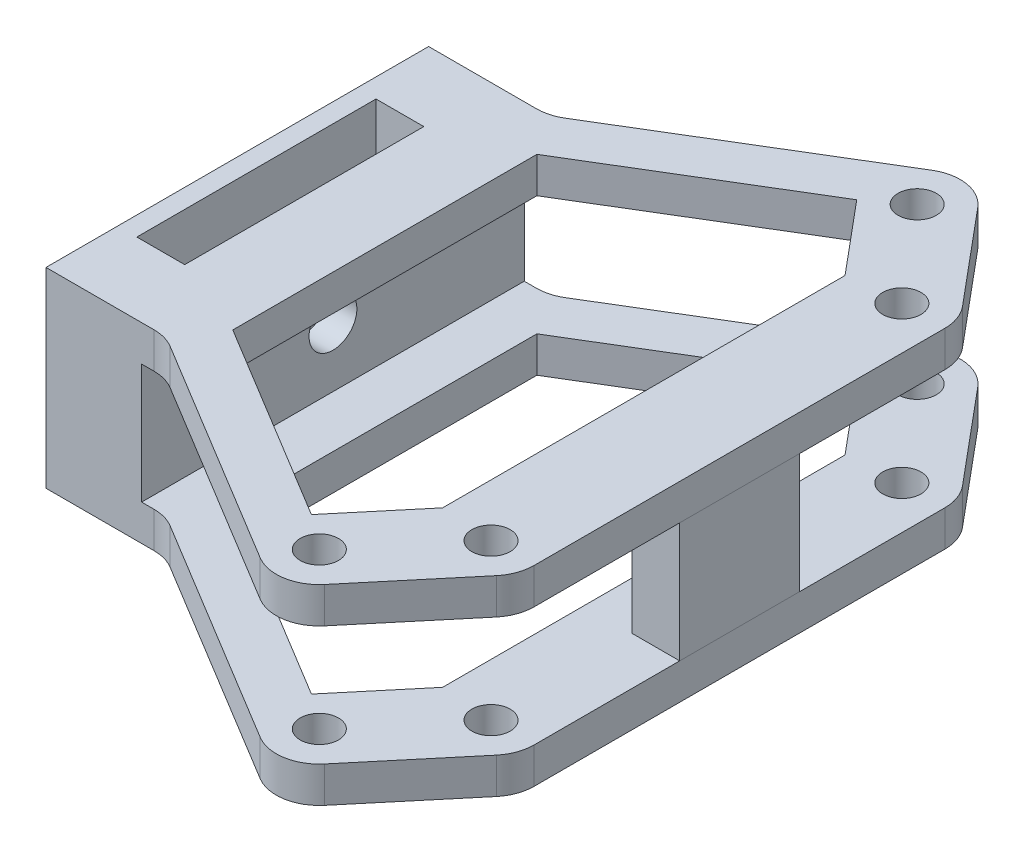
SolidWorks part; units mm, degrees
ref_plane "Front Plane" through (0, 0, 0) normal (0, 0, 1) x (1, 0, 0)
ref_plane "Top Plane" through (0, 0, 0) normal (0, 1, 0) x (1, 0, 0)
ref_plane "Right Plane" through (0, 0, 0) normal (1, 0, 0) x (0, 0, -1)
sketch "Sketch2" plane through (0, 0, 0) normal (0, 1, 0) x (1, 0, 0)
  line L0 (0, 0) -> (-170.473, 0) construction
  line L1 (0, -42.95) -> (0, 42.95)
  line L2 (-2.0962, 48.7238) -> (-18.4462, 68.2738)
  line L3 (-30.0101, 70.1996) -> (-77.759, 41.3004)
  line L4 (-82.419, 40) -> (-105, 40)
  line L5 (-105, 40) -> (-105, -40)
  line L6 (-74.15, -31.7958) -> (-74.15, 31.7958)
  line L7 (-74.15, 31.7958) -> (-32.4907, 57.0093)
  line L8 (-32.4907, 57.0093) -> (-20, 42.074)
  line L9 (-20, 42.074) -> (-20, -42.074)
  line L10 (-82.419, -40) -> (-105, -40)
  line L11 (-32.4907, -57.0093) -> (-20, -42.074)
  line L12 (-74.15, -31.7958) -> (-32.4907, -57.0093)
  line L13 (-30.0101, -70.1996) -> (-77.759, -41.3004)
  line L14 (-2.0962, -48.7238) -> (-18.4462, -68.2738)
  line L16 (-101, -25) -> (-91, -25)
  line L17 (-101, -25) -> (-101, 25)
  line L18 (-101, 25) -> (-91, 25)
  line L19 (-91, -25) -> (-91, 25)
  arc A0 (-2.0962, 48.7238) -> (0, 42.95) centre (-9, 42.95) cw
  arc A1 (-30.0101, 70.1996) -> (-18.4462, 68.2738) centre (-25.35, 62.5) cw
  arc A2 (-77.759, 41.3004) -> (-82.419, 40) centre (-82.419, 49) cw
  arc A3 (-77.759, -41.3004) -> (-82.419, -40) centre (-82.419, -49) ccw
  arc A4 (-30.0101, -70.1996) -> (-18.4462, -68.2738) centre (-25.35, -62.5) ccw
  arc A5 (-2.0962, -48.7238) -> (0, -42.95) centre (-9, -42.95) ccw
  circle A6 centre (-25.35, 62.5) radius 4
  circle A7 centre (-9, 42.95) radius 4
  circle A8 centre (-9, -42.95) radius 4
  circle A9 centre (-25.35, -62.5) radius 4
  point P14 (-80, -40.3312)
  point P16 (-80, 40.3312)
  point P30 (-20, 0)
  point P32 (-74.15, 0)
  dimension "D3" = 9
  dimension "D9" = 85.9
  dimension "D13" = 8
  dimension "D14" = 8
  dimension "D2" = 50
  dimension "D4" = 54.15
  dimension "D5" = 20
  dimension "D6" = 18
  dimension "D7" = 10
  dimension "D8" = 10
  dimension "D10" = 16.35
  dimension "D11" = 19.55
  dimension "D12" = 4
  dimension "80" = 80
extrude "Boss-Extrude1" add sketch "Sketch2" along normal blind 20 and the other way blind 20
sketch "Sketch3" plane through (0, 0, 0) normal (0, 0, 1) x (1, 0, 0)
  line L0 (0, -20) -> (0, 20) construction
  line L1 (-85, 12.5) -> (0, 12.5)
  line L2 (-85, 12.5) -> (-85, -12.5)
  line L3 (-85, -12.5) -> (0, -12.5)
  line L4 (0, 12.5) -> (0, -12.5)
  line L5 (-85, 12.5) -> (0, -12.5) construction
  line L6 (-85, -12.5) -> (0, 12.5) construction
  point P0 (-42.5, 0)
  point P6 (0, 0)
  dimension "D1" = 85
  dimension "D2" = 0
  dimension "D3" = 25
extrude "Cut-Extrude1" cut sketch "Sketch3" against normal through all both and the other way through all
sketch "Sketch4" plane through (0, 0, 0) normal (1, 0, 0) x (0, 0, -1)
  line L0 (42.95, 12.5) -> (-42.95, 12.5) construction
  line L1 (12.5, -12.5) -> (-12.5, -12.5)
  line L2 (12.5, -12.5) -> (12.5, 12.5)
  line L3 (12.5, 12.5) -> (-12.5, 12.5)
  line L4 (-12.5, -12.5) -> (-12.5, 12.5)
  line L5 (12.5, -12.5) -> (-12.5, 12.5) construction
  line L6 (12.5, 12.5) -> (-12.5, -12.5) construction
  point P0 (0, 0)
  dimension "D1" = 25
extrude "Boss-Extrude2" add sketch "Sketch4" against normal blind 10 separate body
hole_wizard "Hole1" positions "Sketch5" profile "Sketch6" legacy
sketch "Sketch5" plane through (-105, 0, 0) normal (-1, 0, 0) x (0, 0, 1)
  point P0 (0, 0)
sketch "Sketch6" plane through (-105, 0, 0) normal (0, 1, 0) x (0, 0, 1)
  line L0 (0, 0) -> (0, 30)
  line L1 (0, 30) -> (5, 30)
  line L2 (5, 30) -> (5, 3)
  line L3 (5, 3) -> (12, 3)
  line L4 (12, 3) -> (12, 0)
  line L5 (12, 0) -> (0, 0)
  line L6 (0, 110) -> (0, -10) construction
  dimension "Diameter" = 10
  dimension "Depth" = 30
  dimension "C-Bore Diameter" = 24
  dimension "C-Bore Depth" = 3
